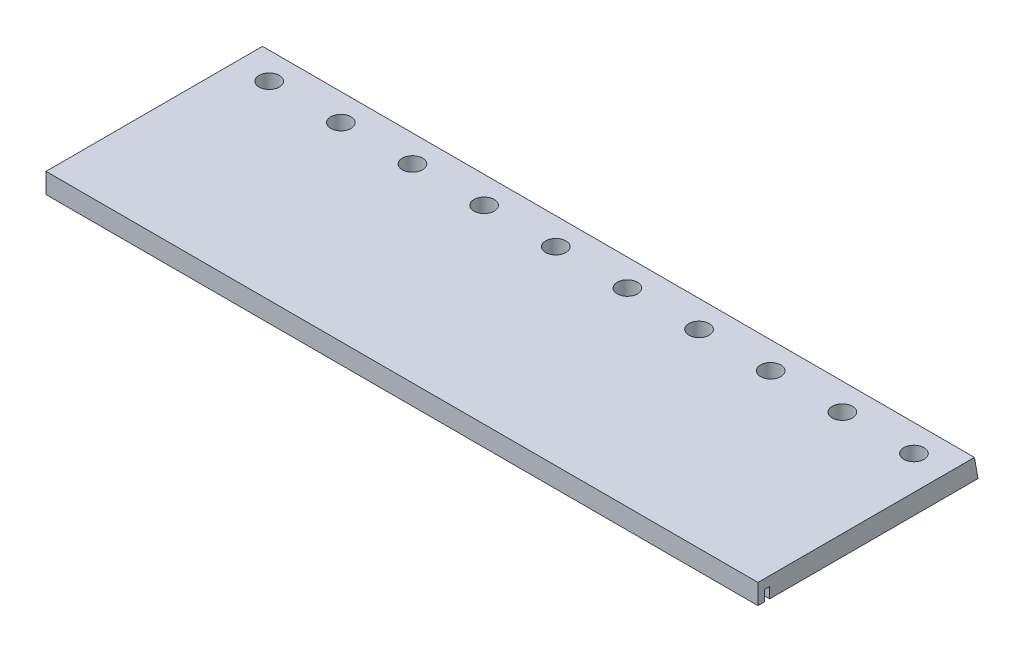
SolidWorks part; units mm, degrees
ref_plane "Front Plane" through (0, 0, 0) normal (0, 0, 1) x (1, 0, 0)
ref_plane "Top Plane" through (0, 0, 0) normal (0, 1, 0) x (1, 0, 0)
ref_plane "Right Plane" through (0, 0, 0) normal (1, 0, 0) x (0, 0, -1)
sketch "Sketch1" plane through (0, 0, 0) normal (0, 1, 0) x (1, 0, 0)
  line L1 (336.55, 104.013) -> (-336.55, 104.013)
  line L2 (336.55, 104.013) -> (336.55, -104.013)
  line L3 (336.55, -104.013) -> (-336.55, -104.013)
  line L4 (-336.55, 104.013) -> (-336.55, -104.013)
  line L5 (336.55, 104.013) -> (-336.55, -104.013) construction
  line L6 (336.55, -104.013) -> (-336.55, 104.013) construction
  point P0 (0, 0)
  dimension "D1" = 673.1
  dimension "D2" = 208.026
extrude "Boss-Extrude1" add sketch "Sketch1" along normal mid plane 19.05
sketch "Sketch2" plane through (0, 9.525, 0) normal (0, 1, 0) x (1, 0, 0)
  line L0 (0, 0) -> (0, 104.013) construction
  line L1 (336.55, 104.013) -> (-336.55, 104.013) construction
  line L2 (-304.8, 75.254) -> (-25.4, 75.254) construction
  line L3 (336.55, 100.654) -> (-336.55, 100.654) construction
  line L4 (304.8, 101.2138) -> (304.8, 50.7401) construction
  circle A2 centre (-304.8, 75.254) radius 9.5846
  circle A12 centre (-237.0709, 75.254) radius 9.5846
  circle A13 centre (-169.3418, 75.254) radius 9.5846
  circle A14 centre (-101.6127, 75.254) radius 9.5846
  circle A15 centre (-33.8836, 75.254) radius 9.5846
  circle A16 centre (33.8455, 75.254) radius 9.5846
  circle A17 centre (101.5746, 75.254) radius 9.5846
  circle A18 centre (169.3037, 75.254) radius 9.5846
  circle A19 centre (237.0328, 75.254) radius 9.5846
  circle A20 centre (304.7619, 75.254) radius 9.5846
  dimension "D2" = 25.4
  dimension "D3" = 304.8
  dimension "D1" = 19.1692
  dimension "D5" = 10
  dimension "D4" = 304.8
extrude "Cut-Extrude1" cut sketch "Sketch2" against normal through all both and the other way through all
sketch "Sketch3" plane through (0, 9.525, 0) normal (0, 1, 0) x (1, 0, 0)
  line L0 (-336.55, 104.013) -> (-336.55, -104.013) construction
  line L1 (-336.55, 84.963) -> (-344.4875, 84.963)
  line L2 (-336.55, 84.963) -> (-336.55, -84.963)
  line L3 (-336.55, -84.963) -> (-344.4875, -84.963)
  line L4 (-344.4875, 84.963) -> (-344.4875, -84.963)
  line L5 (336.55, 104.013) -> (-336.55, 104.013) construction
  line L6 (-336.55, -104.013) -> (336.55, -104.013) construction
  line L7 (0, 0) -> (0, 104.013) construction
  line L8 (344.4875, 84.963) -> (344.4875, -84.963)
  line L9 (336.55, -84.963) -> (344.4875, -84.963)
  line L10 (336.55, 84.963) -> (336.55, -84.963)
  line L11 (336.55, 84.963) -> (344.4875, 84.963)
  dimension "D1" = 19.05
  dimension "D2" = 19.05
  dimension "D3" = 7.9375
extrude "Boss-Extrude2" [suppressed] add sketch "Sketch3" against normal up to surface (19.05 mm away) up to face at (-304.8, -9.525, -65.6694)
sketch "Sketch4" plane through (0, -9.525, 0) normal (0, -1, 0) x (1, 0, 0)
  line L1 (336.55, 97.7119) -> (-336.55, 97.7119)
  line L2 (336.55, 97.7119) -> (336.55, 93.0129)
  line L3 (336.55, 93.0129) -> (-336.55, 93.0129)
  line L4 (-336.55, 97.7119) -> (-336.55, 93.0129)
  line L5 (-336.55, -104.013) -> (-336.55, 104.013) construction
  line L6 (336.55, 104.013) -> (336.55, -104.013) construction
  line L7 (-336.55, 104.013) -> (336.55, 104.013) construction
  dimension "D1" = 6.3011
  dimension "D2" = 4.699
extrude "Cut-Extrude2" cut sketch "Sketch4" against normal blind 10.16
fillet "Fillet1" [suppressed] radius 6.35
sketch "Sketch6" plane through (0, 0, 0) normal (1, 0, 0) x (0, 0, -1)
  line L0 (104.013, -9.525) -> (104.013, 9.525)
  line L1 (104.013, 9.525) -> (100.654, 9.525)
  line L3 (100.654, 9.525) -> (104.013, -9.525)
  dimension "D1" = 10
extrude "Cut-Extrude4" cut sketch "Sketch6" against normal through all both and the other way through all
sketch "Sketch7" plane through (0, -9.525, 0) normal (0, -1, 0) x (1, 0, 0)
  line L0 (-323.0562, -32.6157) -> (323.0562, -32.6157) construction
  line L3 (-323.0562, -24.6147) -> (323.0562, -24.6147)
  line L4 (-323.0562, -40.6167) -> (323.0562, -40.6167)
  line L5 (0, 0) -> (0, -32.6157) construction
  line L6 (-336.55, 104.013) -> (336.55, 104.013) construction
  arc A0 (-323.0562, -24.6147) -> (-323.0562, -40.6167) centre (-323.0562, -32.6157) ccw
  arc A1 (323.0562, -40.6167) -> (323.0562, -24.6147) centre (323.0562, -32.6157) ccw
  point P6 (0, -32.6157)
  dimension "D1" = 16.002
  dimension "D2" = 646.1125
  dimension "D3" = 136.6287
extrude "Cut-Extrude5" cut sketch "Sketch7" against normal blind 7.9375
